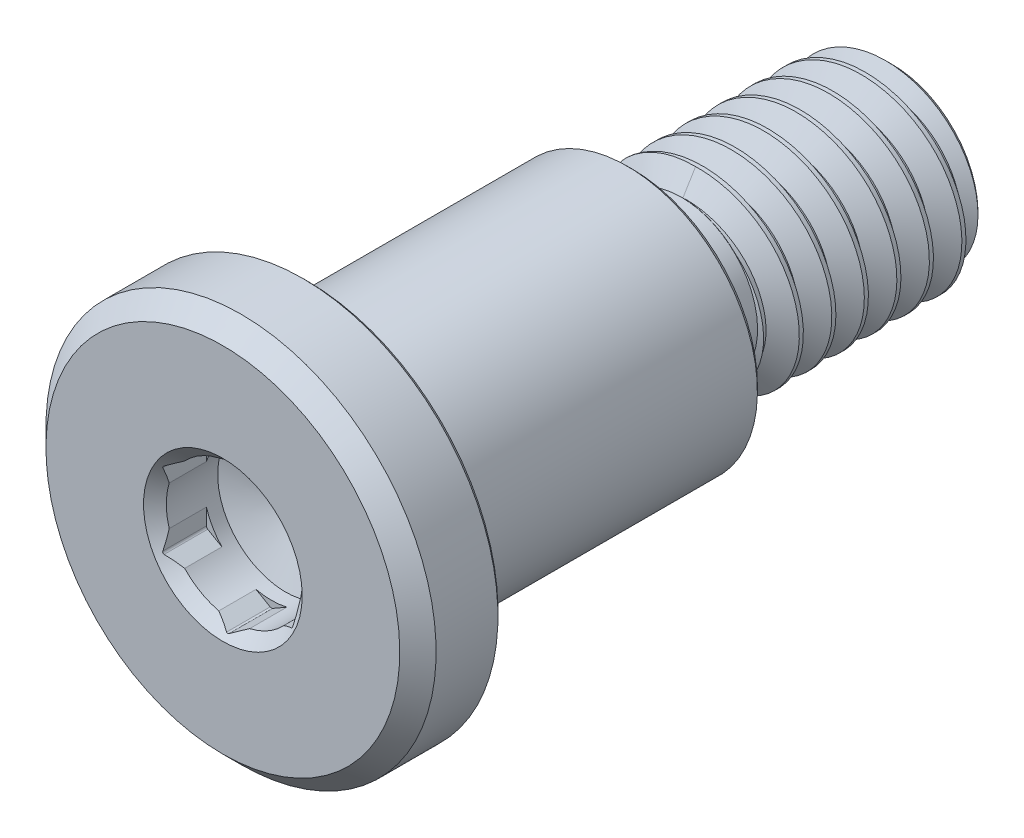
SolidWorks part; units mm, degrees
ref_plane "Front Plane" through (0, 0, 0) normal (0, 0, 1) x (1, 0, 0)
ref_plane "Top Plane" through (0, 0, 0) normal (0, 1, 0) x (1, 0, 0)
ref_plane "Right Plane" through (0, 0, 0) normal (1, 0, 0) x (0, 0, -1)
sketch "Sketch1" plane through (0, 0, 0) normal (1, 0, 0) x (0, 0, -1)
  line L0 (9, 0) -> (0, 0) construction
  line L1 (0, 0) -> (-1.3, 0) construction
  line L2 (-1.3, 3) -> (-1.3, -3) construction
  line L3 (0, 3) -> (0, -3) construction
  line L4 (5, 1.5) -> (9, 1.5) construction
  line L5 (8.9688, 1.5541) -> (9.4688, 1.5541) construction
  line L6 (9.4688, 1.5541) -> (9.2188, 1.1211) construction
  line L7 (9.2188, 1.1211) -> (8.9688, 1.5541) construction
  line L8 (9, 1.5) -> (9.4375, 1.5) construction
  line L9 (9.1875, 1.1752) -> (9.25, 1.1752) construction
  line L10 (9.2188, 1.1211) -> (9.2188, 1.1752) construction
  line L11 (9.2188, 1.5) -> (9.2188, 1.5541) construction
  line L12 (-1.3, 1) -> (-0.335, 1) construction
  line L13 (-0.335, 1) -> (-0.335, -1) construction
  line L14 (-0.335, -1) -> (-1.3, -1) construction
  line L15 (5, 2) -> (5, -2) construction
  line L16 (-1.3, 3) -> (0, 3) construction
  line L17 (5, -1.5) -> (9, -1.5) construction
  point P12 (-0.335, 0)
  point P27 (5, 0)
  point P36 (8.25, -1.5)
  dimension "Screw Size Decimal Equivalent" = 3
  dimension "Thread Length" = 4
  dimension "Shoulder Diameter" = 4
  dimension "Head Height" = 1.3
  dimension "Head Diameter" = 6
  dimension "Drive Size" = 2
  dimension "Thread Pitch" = 0.5
  dimension "Pitch/8" = 0.0625
  dimension "Thread Note" = 0.75
  dimension "Shoulder Length" = 5
  dimension "Approximate Drive Depth" = 0.965
sketch "Sketch2" plane through (0, 0, 0) normal (1, 0, 0) x (0, 0, -1)
  line L0 (-1.3, 3) -> (0, 3)
  line L1 (0, 3) -> (0, 2)
  line L2 (0, 2) -> (5, 2)
  line L3 (5, 2) -> (5, 1.5)
  line L4 (5, 1.5) -> (9, 1.5)
  line L5 (9, 1.5) -> (9, 0)
  line L6 (9, 0) -> (-1.3, 0)
  line L7 (-1.3, 0) -> (-1.3, 3)
revolve "Revolve1" add sketch "Sketch2" angle 360 about L1
chamfer "Chamfer1" distance 0.2795 angle 45 1 edges at (0, 3, 1.3)
chamfer "Chamfer4" distance 0.0699 angle 45 1 edges at (0, 3, 0)
sketch "Sketch3" plane through (0, 0, 0) normal (1, 0, 0) x (0, 0, -1)
  line L0 (0, 2) -> (0.4249, 2)
  line L1 (5, 2) -> (0, 2) construction
  line L2 (0.4249, 2) -> (0.3005, 1.8755)
  line L3 (0, 3) -> (0, -3) construction
  line L4 (0, 1.824) -> (0.176, 1.824) construction
  arc A0 (0.3005, 1.8755) -> (0, 2) centre (0.176, 2) cw
  dimension "D2" = 0.176
  dimension "D1" = 45
revolve "Cut-Revolve1" cut sketch "Sketch3" angle 360 about L0
sketch "Sketch4" plane through (0, 0, 0) normal (1, 0, 0) x (0, 0, -1)
  line L0 (5, 1.5) -> (9, 1.5) construction
  line L1 (5, 1.5) -> (5.939, 1.5)
  line L2 (5, 1.5) -> (5, 1.1727)
  line L3 (5, 1.1727) -> (5.75, 1.1727)
  line L4 (5.939, 1.5) -> (5.75, 1.1727)
  line L5 (5, 2) -> (5, -2) construction
  line L7 (9.1875, 1.1752) -> (9.25, 1.1752) construction
  point P8 (5.7515, 1.1752)
  dimension "D1" = 0.75
  dimension "D2" = 60
  dimension "D3" = 0.0025
revolve "Cut-Revolve2" cut sketch "Sketch4" angle 360 about L0
chamfer "Chamfer2" distance 0.08 angle 45 1 edges at (0, 2, -5)
fillet "Fillet1" radius 0.064 1 edges at (0, 1.1727, -5)
chamfer "Chamfer3" distance 0.1875 angle 45 1 edges at (0, 1.5, -9)
sketch "Sketch11" plane through (0, 0, 1.3) normal (0, 0, 1) x (1, 0, 0)
  circle A0 centre (0, 0) radius 1.045
  dimension "D1" = 2.09
extrude "Cut-Extrude4" cut sketch "Sketch11" against normal up to vertex (0.965 mm away) up to point (0, 1, 0.335)
sketch "Sketch5" plane through (0, 0, 1.3) normal (0, 0, 1) x (1, 0, 0)
  line L1 (0, 1.1547) -> (-1, 0.5774)
  line L2 (-1, 0.5774) -> (-1, -0.5774)
  line L3 (-1, -0.5774) -> (0, -1.1547)
  line L4 (0, -1.1547) -> (1, -0.5774)
  line L5 (1, -0.5774) -> (1, 0.5774)
  line L6 (1, 0.5774) -> (0, 1.1547)
  circle A0 centre (0, 0) radius 1 construction
  circle A1 centre (0, 0) radius 3 construction
extrude "Cut-Extrude1" cut sketch "Sketch5" against normal blind 0.7469
sketch "Sketch6" plane through (0, 0, 1.3) normal (0, 0, 1) x (1, 0, 0)
  circle A0 centre (0, 0) radius 1.22
  dimension "D1" = 2.44
extrude "Cut-Extrude2" cut sketch "Sketch6" against normal up to vertex (0.965 mm away) draft 45 up to point (0, 1, 0.335)
sketch "Sketch9" plane through (0, 0, 0.335) normal (0, 0, 1) x (1, 0, 0)
  circle A0 centre (0, 0) radius 1.045
  circle A2 centre (0, 0) radius 1.045 construction
extrude "Cut-Extrude3" cut sketch "Sketch9" against normal through all draft 70
fillet "Fillet2" radius 0.04 6 edges at (1, 0.5774, 0.8939) (0, 1.1547, 0.8939) (-1, 0.5774, 0.8939) (0, -1.1547, 0.8939) (1, -0.5774, 0.8939) (-1, -0.5774, 0.8939)
fillet "Fillet3" radius 0.2499 1 edges at (0, 2, -0.4249)
ref_plane "Plane1" through (0, 0, -5.75) normal (0, 0, 1) x (1, 0, 0)
split "Split1" trim tools "Plane1" bodies to split 113 resulting bodies 109 110
sketch "Sketch7" plane through (0, 0, 0) normal (1, 0, 0) x (0, 0, -1)
  line L0 (9.1875, 1.1752) -> (9.25, 1.1752)
  line L1 (9.25, 1.1752) -> (9.4531, 1.5271)
  line L2 (9.4688, 1.5541) -> (9.2188, 1.1211) construction
  line L3 (9.4531, 1.5271) -> (8.9844, 1.5271)
  line L4 (9.2188, 1.1211) -> (8.9688, 1.5541) construction
  line L5 (8.9844, 1.5271) -> (9.1875, 1.1752)
  line L6 (9.2188, 1.5) -> (9.2188, 1.5541) construction
  point P12 (9.2188, 1.5271)
sketch "Sketch8" plane through (0, 0, -9) normal (0, 0, -1) x (-1, 0, 0)
  circle A0 centre (0, 0) radius 1.5
curve "Helix/Spiral1" pitch 0.5 height 3.75 radius 1.5 centre (0, 0, -9) axis (0, 0, 1) start towards (0, 1, 0)
sweep "Cut-Sweep1" cut profiles "Sketch7" path "Helix/Spiral1" align with end faces yes
ref_plane "Plane2" through (0, 0, -5.7515) normal (0, 0, 1) x (1, 0, 0)
sketch "Sketch10" plane through (0, 0, -5.7515) normal (0, 0, 1) x (1, 0, 0)
  circle A0 centre (0, 0) radius 1.1752
extrude "Boss-Extrude1" add sketch "Sketch10" along normal through all draft 60
equation "\"Pitch/8@Sketch1\" = \"Thread Pitch@Sketch1\" / 8"
equation "\"Thread Note@Sketch1\"=\"Thread Pitch@Sketch1\"*1.5"
equation "\"D1@Chamfer1\"=\"Head Height@Sketch1\"*.215"
equation "\"D1@Sketch4\"=\"Thread Pitch@Sketch1\"*1.5"
equation "\"D1@Chamfer2\"=\"Shoulder Diameter@Sketch1\"*.02"
equation "\"D1@Fillet1\" = \"D1@Chamfer2\" * .8"
equation "\"D1@Chamfer3\"=\"Thread Pitch@Sketch1\" * .375"
equation "\"D1@Sketch6\"=\"Drive Size@Sketch1\" * 1.22"
equation "\"D1@Fillet2\"=\"Drive Size@Sketch1\"*.02"
equation "\"D4@Helix/Spiral1\"=\"Thread Pitch@Sketch1\""
equation "\"D3@Helix/Spiral1\"=\"Thread Length@Sketch1\" - \"Thread Pitch@Sketch1\"*.5"
equation "\"Approximate Drive Depth@Sketch1\"=\"Drive Size@Sketch1\"*.4825"
equation "\"D1@Chamfer4\"=\"D1@Chamfer1\"*.25"
equation "\"D2@Sketch3\"=\"Shoulder Diameter@Sketch1\"*.044"
equation "\"D1@Fillet3\"=\"D2@Sketch3\" * 1.42"
equation "\"D1@Sketch11\"=\"Drive Size@Sketch1\"*1.045"
equation "\"D1@Cut-Extrude1\"=\"Approximate Drive Depth@sketch1\"*.774"
